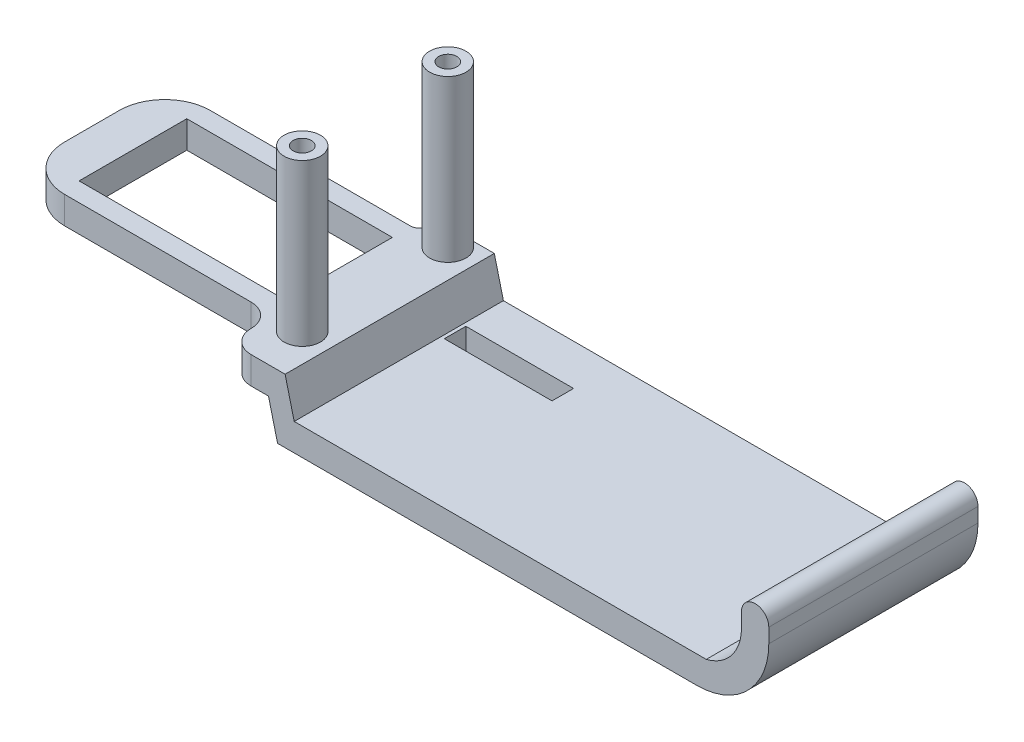
SolidWorks part; units mm, degrees
material "ABS"
ref_plane "Front" through (0, 0, 0) normal (0, 0, 1) x (1, 0, 0)
ref_plane "Top" through (0, 0, 0) normal (0, 1, 0) x (1, 0, 0)
ref_plane "Right" through (0, 0, 0) normal (1, 0, 0) x (0, 0, -1)
sketch "Sketch1" plane through (0, 0, 0) normal (0, 1, 0) x (1, 0, 0)
  line L0 (4.5, 8) -> (27.1, 8) construction
  line L1 (4.5, 13.92) -> (27.1, 13.92)
  line L2 (4.5, 13.92) -> (4.5, 2.08)
  line L3 (4.5, 2.08) -> (27.1, 2.08)
  line L4 (27.1, 13.92) -> (27.1, 2.08)
  line L6 (0, 16) -> (28, 16)
  line L7 (0, 16) -> (0, 0)
  line L8 (0, 0) -> (28, 0)
  line L9 (28, 16) -> (28, 0)
  dimension "D1" = 16
  dimension "D2" = 28
  dimension "D5" = 22.6
  dimension "D3" = 4.5
  dimension "D4" = 11.84
extrude "Boss-Extrude1" add sketch "Sketch1" along normal blind 3 contours L9 L6 L7 L8 | L9 | L9 region at (14, 0, -15.6775)
sketch "Esquisse1" plane through (0, 0, 0) normal (0, 0, 1) x (1, 0, 0)
  line L0 (34.2269, 3) -> (35.2269, -1)
  line L1 (35.2269, -1) -> (62.4, -1)
  line L2 (62.4, -1) -> (62.4, -4)
  line L3 (62.4, -4) -> (33.4, -4)
  line L4 (33.4, -4) -> (32.4, 0)
  line L5 (28, 0) -> (32.4, 0)
  line L11 (28, 3) -> (34.2269, 3)
  line L12 (28, 3) -> (28, 0)
  dimension "D1" = 3
  dimension "D2" = 30
  dimension "D3" = 1
  dimension "D4" = 4
  dimension "D5" = 2.5
  dimension "D6" = 4.4
extrude "Boss.-Extru.1" add sketch "Esquisse1" against normal blind 18 and the other way blind 5 contours L4 L5 L12 L11 L0 L1 L2 L3
sketch "Esquisse6" plane through (0, 3, 0) normal (0, 1, 0) x (1, 0, 0)
  line L0 (4.5, 8) -> (27.1, 8) construction
  line L1 (4.5, 13.92) -> (4.5, 2.08) construction
  line L2 (27.1, 13.92) -> (27.1, 2.08) construction
  line L5 (31.1135, 0) -> (31.1135, 16) construction
  line L6 (28, 16) -> (28, 18) construction
  line L7 (34.2269, -5) -> (34.2269, 18) construction
  circle A1 centre (31.1135, 0) radius 2
  circle A3 centre (31.1135, 16) radius 2
  dimension "D1" = 16
  dimension "D2" = 4
  dimension "D3" = 4
extrude "Boss.-Extru.3" add sketch "Esquisse6" along normal blind 17.7
sketch "Esquisse7" plane through (0, 20.7, 0) normal (0, 1, 0) x (1, 0, 0)
  circle A0 centre (31.1135, 16) radius 1
  circle A1 centre (31.1135, 0) radius 1
  circle A2 centre (31.1135, 0) radius 2 construction
  dimension "D1" = 2
  dimension "D2" = 2
extrude "Enlèv. mat.-Extru.3" cut sketch "Esquisse7" against normal blind 4
sketch "Esquisse8" plane through (0, -1, 0) normal (0, 1, 0) x (1, 0, 0)
  line L0 (35.2269, 18) -> (62.4, 18) construction
  line L1 (35.6, 13.5) -> (47.44, 13.5)
  line L2 (35.6, 13.5) -> (35.6, 11.13)
  line L3 (35.6, 11.13) -> (47.44, 11.13)
  line L4 (47.44, 13.5) -> (47.44, 11.13)
  line L6 (28, 16) -> (28, 18) construction
  dimension "D1" = 4.5
  dimension "D2" = 2.37
  dimension "D3" = 11.84
  dimension "D4" = 7.6
extrude "Enlèv. mat.-Extru.4" cut sketch "Esquisse8" against normal blind 10
fillet "Congé1" radius 1 2 edges at (28, 1.5, -18)
fillet "Congé3" radius 5 2 edges at (0, 1.5, 0) (0, 1.5, -16)
fillet "Congé4" radius 2.5 2 edges at (28, 1.5, 5)
sketch "Esquisse14" plane through (62.4, 0, 0) normal (1, 0, 0) x (0, 0, -1)
  line L0 (-5, -2.5) -> (18, -2.5) construction
  line L1 (-5, -1) -> (-5, -4) construction
  line L2 (18, -1) -> (18, -4) construction
ref_plane "Plan1" through (70.4, 0, 0) normal (1, 0, 0) x (0, 0, -1)
ref_plane "Plan2" through (0, 0, -6.5) normal (0, 0, -1) x (-1, 0, 0)
ref_plane "Plan3" through (0, -2.5, 0) normal (0, -1, 0) x (-1, 0, 0)
sketch "Esquisse18" plane through (62.4, 51.4, 0) normal (-1, 0, 0) x (0, -1, 0)
  line L1 (52.4, -18) -> (55.4, -18)
  line L2 (52.4, -18) -> (52.4, 5)
  line L3 (52.4, 5) -> (55.4, 5)
  line L4 (55.4, -18) -> (55.4, 5)
  line L6 (55.4, 5) -> (55.4, -18) construction
  line L7 (52.4, -18) -> (55.4, -18) construction
  line L8 (52.4, 5) -> (55.4, 5) construction
  dimension "D1" = 3
ref_plane "Plan4" through (0, 0, 11.5) normal (0, 0, 1) x (1, 0, 0)
sketch "Sketch3" plane through (0, 0, 5) normal (0, 0, 1) x (1, 0, 0)
  line L0 (62.4, -4) -> (79.4806, -4)
  line L1 (76.4, 3.5437) -> (76.4, 5.5)
  line L2 (76.4, 5.5) -> (79.4, 5.5) construction
  line L3 (79.4, 5.5) -> (79.4, -1)
  line L4 (79.4, -1) -> (80.5281, -1)
  line L5 (87.4, 3.9194) -> (84.4, 3.9194) construction
  line L6 (84.4, 3.9194) -> (84.4, 5.5)
  line L7 (84.4, 5.5) -> (87.4, 5.5) construction
  line L8 (87.4, 5.5) -> (87.4, 3.9194)
  line L9 (62.4, -1) -> (62.4, -4)
  line L10 (62.4, -1) -> (71.8563, -1)
  line L11 (35.2269, -1) -> (62.4, -1) construction
  line L12 (71.8563, -1) -> (79.4, -1)
  arc A0 (71.8563, -1) -> (76.4, 3.5437) centre (71.8563, 3.5437) ccw
  arc A1 (79.4806, -4) -> (87.4, 3.9194) centre (79.4806, 3.9194) ccw
  arc A2 (80.5281, -1) -> (84.4, 3.9194) centre (79.3389, 3.9194) ccw
  arc A3 (76.4, 5.5) -> (79.4, 5.5) centre (77.9, 5.5) cw
  arc A4 (84.4, 5.5) -> (87.4, 5.5) centre (85.9, 5.5) cw
  point P21 (77.9, 7)
  line M6 (62.4, -4) -> (62.4, -1)
  dimension "D1" = 3
  dimension "D2" = 3
  dimension "D3" = 14
  dimension "D4" = 5
  dimension "D5" = 8
extrude "Boss-Extrude2" add sketch "Sketch3" against normal up to surface (23 mm away) contours A4 L6 A2 L4 L12 L10 L0 A1 L8 M6 region at (76.5822, -1.0207, 5) up to face at (38.7964, -0.1111, -18)
